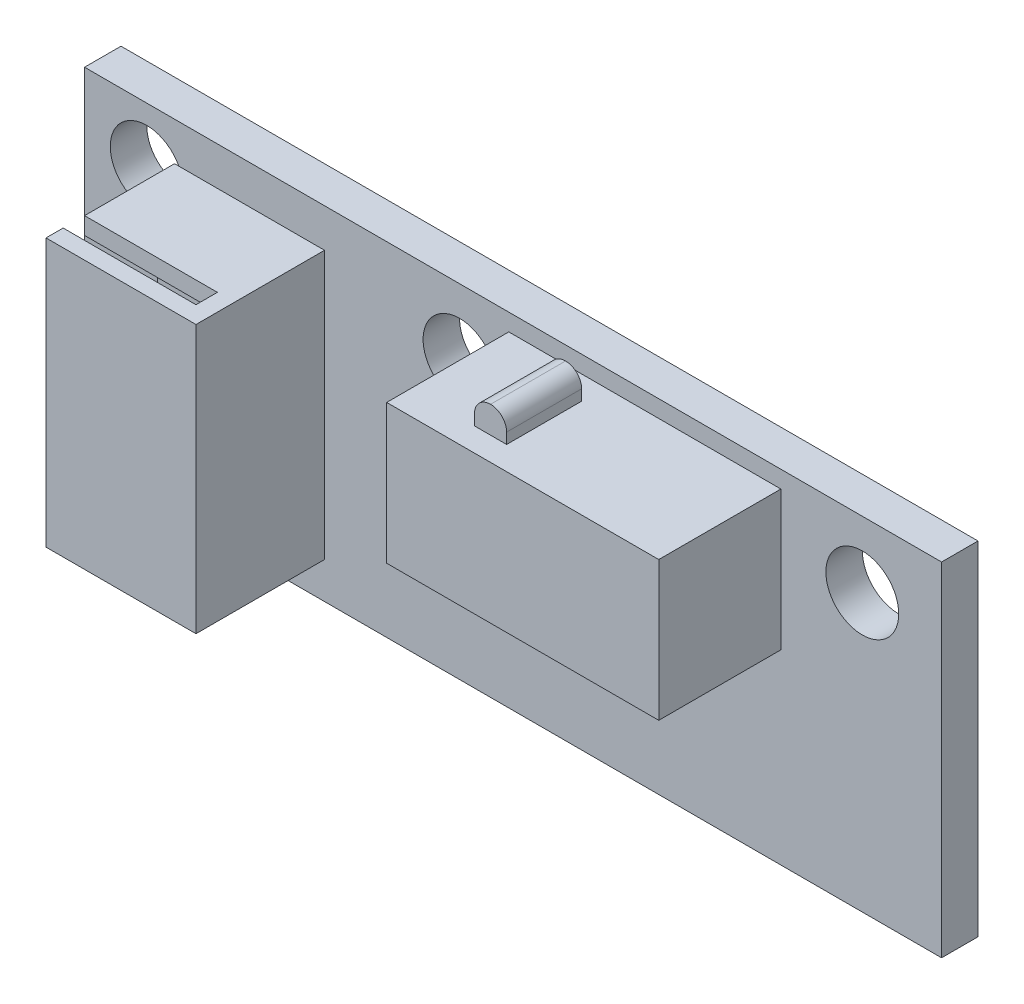
SolidWorks part; units mm, degrees
ref_plane "Front Plane" through (0, 0, 0) normal (0, 0, 1) x (1, 0, 0)
ref_plane "Top Plane" through (0, 0, 0) normal (0, 1, 0) x (1, 0, 0)
ref_plane "Right Plane" through (0, 0, 0) normal (1, 0, 0) x (0, 0, -1)
sketch "Sketch1" plane through (0, 0, 0) normal (0, 0, 1) x (1, 0, 0)
  line L1 (-20, -8) -> (20, -8)
  line L2 (-20, -8) -> (-20, 8)
  line L3 (-20, 8) -> (20, 8)
  line L4 (20, -8) -> (20, 8)
  line L5 (-20, -8) -> (20, 8) construction
  line L6 (-20, 8) -> (20, -8) construction
  point P0 (0, 0)
  dimension "D1" = 40
  dimension "D2" = 16
extrude "Boss-Extrude1" add sketch "Sketch1" along normal blind 1.7
hole_wizard "M3 Clearance Hole1" positions "Sketch2" profile "Sketch3" hole size "M3" standard "ANSI Metric" end condition through all
sketch "Sketch2" plane through (0, 0, 1.7) normal (0, 0, 1) x (1, 0, 0)
  line L0 (20, 8) -> (-20, 8) construction
  line L1 (20, -8) -> (20, 8) construction
  line L3 (-17.1, 5.4) -> (-17.1, -5.4) construction
  line L5 (-20, 8) -> (-20, -8) construction
  point P0 (-17.1, -5.4)
  point P2 (-2.5, 4.9)
  point P4 (16.3, 4.9)
  point P6 (-17.1, 5.4)
  point P26 (-17.1, 0)
  point P29 (-20, 0)
  dimension "D1" = 3.1
  dimension "D2" = 3.7
  dimension "D3" = 18.8
  dimension "D4" = 14.6
  dimension "D5" = 10.8
sketch "Sketch3" plane through (-17.1, -5.4, 1.7) normal (1, 0, 0) x (0, -1, 0)
  line L0 (0, 0) -> (0, 1.7)
  line L1 (0, 1.7) -> (1.7, 1.7)
  line L2 (1.7, 1.7) -> (1.7, 0)
  line L5 (1.7, 0) -> (0, 0)
  line L11 (0, -6.35) -> (0, 107.95) construction
  dimension "Thru Hole Dia." = 3.4
  dimension "Thru Hole Depth" = 1.7
sketch "Sketch5" plane through (0, 0, 1.7) normal (0, 0, 1) x (1, 0, 0)
  line L0 (20, 8) -> (-20, 8) construction
  line L1 (-0.2, 7.2) -> (12.5, 7.2)
  line L2 (-0.2, 7.2) -> (-0.2, 0.7)
  line L3 (-0.2, 0.7) -> (12.5, 0.7)
  line L4 (12.5, 7.2) -> (12.5, 0.7)
  line L5 (-0.2, 7.2) -> (12.5, 0.7) construction
  line L6 (-0.2, 0.7) -> (12.5, 7.2) construction
  line L7 (20, 8) -> (-20, 8)
  line L8 (20, -8) -> (20, 8) construction
  circle A0 centre (16.3, 4.9) radius 1.7 construction
  circle A1 centre (-2.5, 4.9) radius 1.7 construction
  circle A2 centre (16.3, 4.9) radius 1.7
  circle A3 centre (-2.5, 4.9) radius 1.7
  point P4 (6.15, 3.95)
  dimension "D1" = 12.7
  dimension "D2" = 6.5
  dimension "D3" = 0.8
  dimension "D4" = 7.5
extrude "Boss-Extrude2" add sketch "Sketch5" along normal blind 5.7 contours L4 L1 L2 L3 region at (6.15, 3.95, 1.7)
sketch "Sketch6" plane through (0, 7.2, 0) normal (0, 1, 0) x (1, 0, 0)
  line L0 (-0.2, -7.4) -> (-0.2, -1.7) construction
  line L1 (2.8, -2.8) -> (4.3, -2.8)
  line L2 (2.8, -2.8) -> (2.8, -6.3)
  line L3 (2.8, -6.3) -> (4.3, -6.3)
  line L4 (4.3, -2.8) -> (4.3, -6.3)
  line L5 (2.8, -2.8) -> (4.3, -6.3) construction
  line L6 (2.8, -6.3) -> (4.3, -2.8) construction
  line L7 (-0.2, -7.4) -> (-0.2, -1.7)
  point P4 (3.55, -4.55)
  point P7 (-0.2, -4.55)
  point P8 (2.8, -4.55)
  dimension "D1" = 1.5
  dimension "D2" = 3.5
  dimension "D3" = 4.5
extrude "Boss-Extrude3" add sketch "Sketch6" along normal blind 1.25 separate body contours L4 L1 L2 L3 region at (3.55, 7.2, 4.55)
fillet "Fillet1" radius 0.75 2 edges at (4.3, 8.45, 4.55) (2.8, 8.45, 4.55)
sketch "Sketch7" plane through (0, 0, 1.7) normal (0, 0, 1) x (1, 0, 0)
  line L0 (-20, -8) -> (20, -8) construction
  line L1 (-15.8, 6.2) -> (-8.8, 6.2)
  line L2 (-15.8, 6.2) -> (-15.8, -6.3)
  line L3 (-15.8, -6.3) -> (-8.8, -6.3)
  line L4 (-8.8, 6.2) -> (-8.8, -6.3)
  line L5 (-15.8, 6.2) -> (-8.8, -6.3) construction
  line L6 (-15.8, -6.3) -> (-8.8, 6.2) construction
  line L7 (-20, 8) -> (-20, -8) construction
  point P4 (-12.3, -0.05)
  dimension "D1" = 12.5
  dimension "D2" = 7
  dimension "D3" = 1.7
  dimension "D4" = 4.2
extrude "Boss-Extrude4" add sketch "Sketch7" along normal blind 6 separate body
sketch "Sketch8" plane through (-15.8, 0, 0) normal (-1, 0, 0) x (0, 0, 1)
  line L6 (1.7, 6.2) -> (1.7, -6.3)
  line L7 (2.5, -5.5) -> (6.9, -5.5)
  line L8 (6.9, -5.5) -> (6.9, 5.4)
  line L9 (1.7, -6.3) -> (7.7, -6.3)
  line L10 (7.7, -6.3) -> (7.7, 6.2)
  line L11 (7.7, 6.2) -> (1.7, 6.2)
  line L12 (1.7, 6.2) -> (1.7, -6.3)
  line L15 (1.7, -6.3) -> (7.7, -6.3)
  line L16 (7.7, -6.3) -> (7.7, 6.2)
  line L17 (7.7, 6.2) -> (1.7, 6.2)
  line L18 (6.9, 5.4) -> (2.5, 5.4)
  line L19 (6.9, -5.5) -> (5.9, -5.5)
  line L20 (6.9, -5.5) -> (6.9, -6.3)
  line L21 (6.9, -6.3) -> (5.9, -6.3)
  line L22 (5.9, -5.5) -> (5.9, -6.3)
  line L23 (6.9, -5.5) -> (5.9, -6.3) construction
  line L24 (6.9, -6.3) -> (5.9, -5.5) construction
  line L25 (6.9, 5.4) -> (5.9, 5.4)
  line L26 (6.9, 5.4) -> (6.9, 6.2)
  line L27 (6.9, 6.2) -> (5.9, 6.2)
  line L28 (5.9, 5.4) -> (5.9, 6.2)
  line L29 (6.9, 5.4) -> (5.9, 6.2) construction
  line L30 (6.9, 6.2) -> (5.9, 5.4) construction
  line L31 (2.5, 5.4) -> (2.5, -5.5)
  point P15 (6.4, -5.9)
  point P19 (6.4, 5.8)
  dimension "D3" = 1
  dimension "D1" = 0
  dimension "D2" = 0.8
extrude "Cut-Extrude1" cut sketch "Sketch8" against normal offset from surface (6.2 mm away) 0.8 contours L28 L26 L17 | L22 L15 L20 | L18 L31 L7 L8 region at (-15.8, 5.8, 6.4) region at (-15.8, -5.9, 6.4) region at (-15.8, -0.05, 4.7) up to face at (-8.8, -0.05, 4.7)
